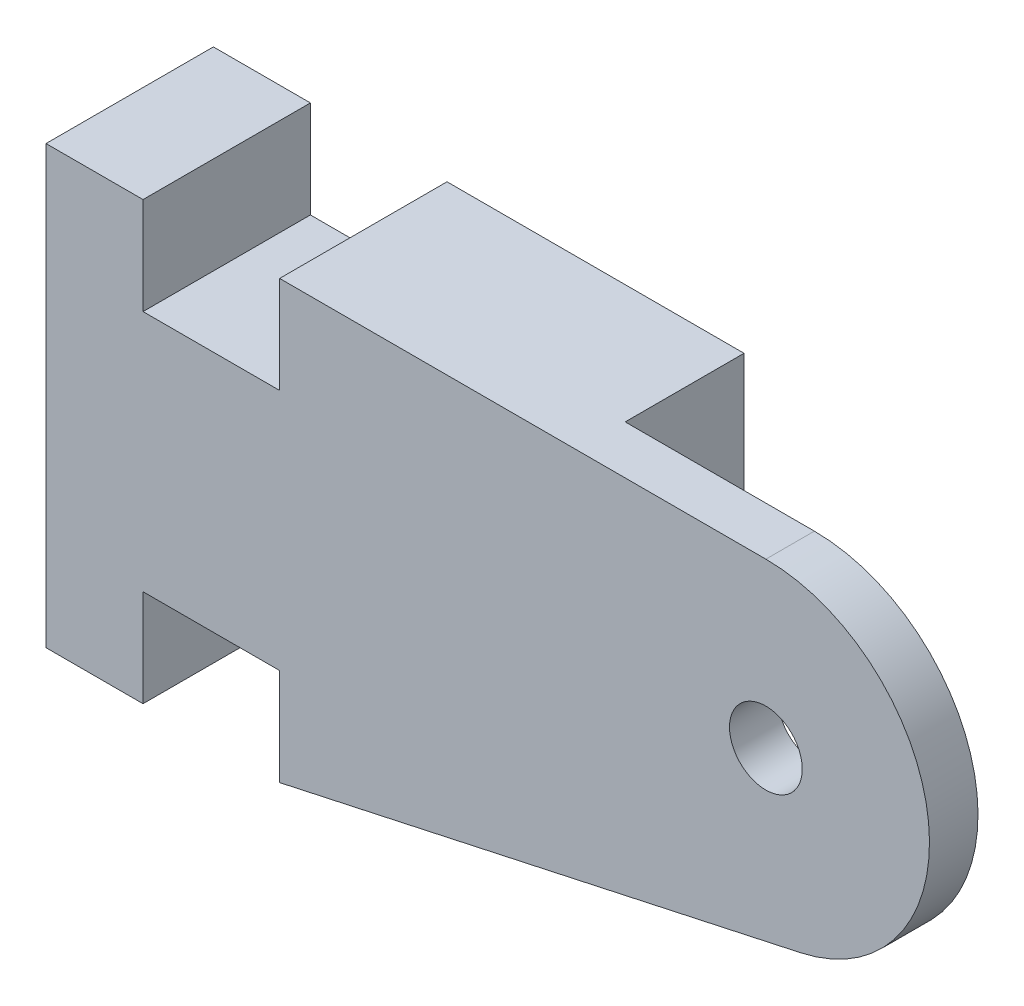
SolidWorks part; units mm, degrees
ref_plane "Front Plane" through (0, 0, 0) normal (0, 0, 1) x (1, 0, 0)
ref_plane "Top Plane" through (0, 0, 0) normal (0, 1, 0) x (1, 0, 0)
ref_plane "Right Plane" through (0, 0, 0) normal (1, 0, 0) x (0, 0, -1)
sketch "Sketch1" plane through (0, 0, 0) normal (0, 0, 1) x (1, 0, 0)
  line L19 (14.2505, 5.9748) -> (15.1187, 10.8988) construction
  line L21 (13.1491, 11.2461) -> (15.1187, 10.8988) construction
  line L22 (12.2808, 6.3221) -> (13.1491, 11.2461) construction
  line L23 (6.2554, 12.4616) -> (8.225, 12.1143) construction
  line L24 (5.3872, 7.5376) -> (6.2554, 12.4616) construction
  line L25 (7.3568, 7.1903) -> (5.3872, 7.5376) construction
  line L26 (7.3568, 7.1903) -> (8.225, 12.1143) construction
  line L27 (14.2505, 5.9748) -> (12.2808, 6.3221) construction
  line L28 (9.6315, 18.0003) -> (29.6765, 18.0003)
  line L29 (0, 0) -> (4, 0)
  line L30 (4, 0) -> (4, 4)
  line L31 (4, 18.0003) -> (4, 14.0003)
  line L32 (0, 18.0003) -> (4, 18.0003)
  line L33 (9.6315, 4) -> (4, 4)
  line L34 (9.6315, 0) -> (9.6315, 4)
  line L35 (9.6315, 0) -> (31.1079, 4.6639)
  line L36 (9.6315, 14.0003) -> (4, 14.0003)
  line L37 (9.6315, 18.0003) -> (9.6315, 14.0003)
  line L38 (0, 18.0003) -> (0, 0)
  circle A2 centre (29.6765, 11.2553) radius 12.12 construction
  circle A3 centre (29.6765, 11.2553) radius 1.5
  arc A4 (29.6765, 18.0003) -> (31.1079, 4.6639) centre (29.6765, 11.2553) cw
  dimension "D1" = 3
  dimension "D2" = 24.24
  dimension "D3" = 6.745
  dimension "D4" = 4
  dimension "D5" = 9.6315
  dimension "D7" = 31.1079
  dimension "ThumbLinkLengthMCP" = 20.045
extrude "Boss-Extrude1" add sketch "Sketch1" along normal blind 6.9
sketch "Sketch4" plane through (0, 0, 0) normal (0, 0, 1) x (1, 0, 0)
  line L0 (21.8765, 2.6592) -> (21.8765, 18.0003)
  line L1 (29.6765, 18.0003) -> (9.6315, 18.0003) construction
  line L2 (21.8765, 18.0003) -> (29.6765, 18.0003)
  line L3 (21.8765, 2.6592) -> (31.1079, 2.6592)
  line L4 (31.1079, 2.6592) -> (31.1079, 4.6639)
  arc A0 (31.1079, 4.6639) -> (29.6765, 18.0003) centre (29.6765, 11.2553) ccw
  dimension "D1" = 21.8765
extrude "Cut-Extrude2" cut sketch "Sketch4" along normal blind 4.9
sketch "Sketch5" plane through (0, 0, 0) normal (-1, 0, 0) x (0, 0, 1)
  circle A1 centre (2.45, 8) radius 1
  dimension "D1" = 8
  dimension "D3" = 2
  dimension "D2" = 2.45
extrude "Cut-Extrude3" cut sketch "Sketch5" against normal blind 14
ref_plane "Plane1" through (19.7462, -5.291, 0) normal (0.9659, -0.2588, 0) x (0, 0, -1)
sketch "Sketch8" plane through (19.7462, -5.291, 0) normal (0.9659, -0.2588, 0) x (0, 0, -1)
  line L2 (-2.45, -5.662) -> (-2.45, 11.2) construction
  circle A0 centre (-2.45, 11.2) radius 1
  dimension "D1" = 2
  dimension "D2" = 11.2
  dimension "D3" = 2.45
extrude "Cut-Extrude5" cut sketch "Sketch8" against normal blind 17
equation "\"ThumbLinkLengthMCP@Sketch1\"= \"HB@parametersSketch@prostheticParameters.SLDPRT\" * 0.211"
